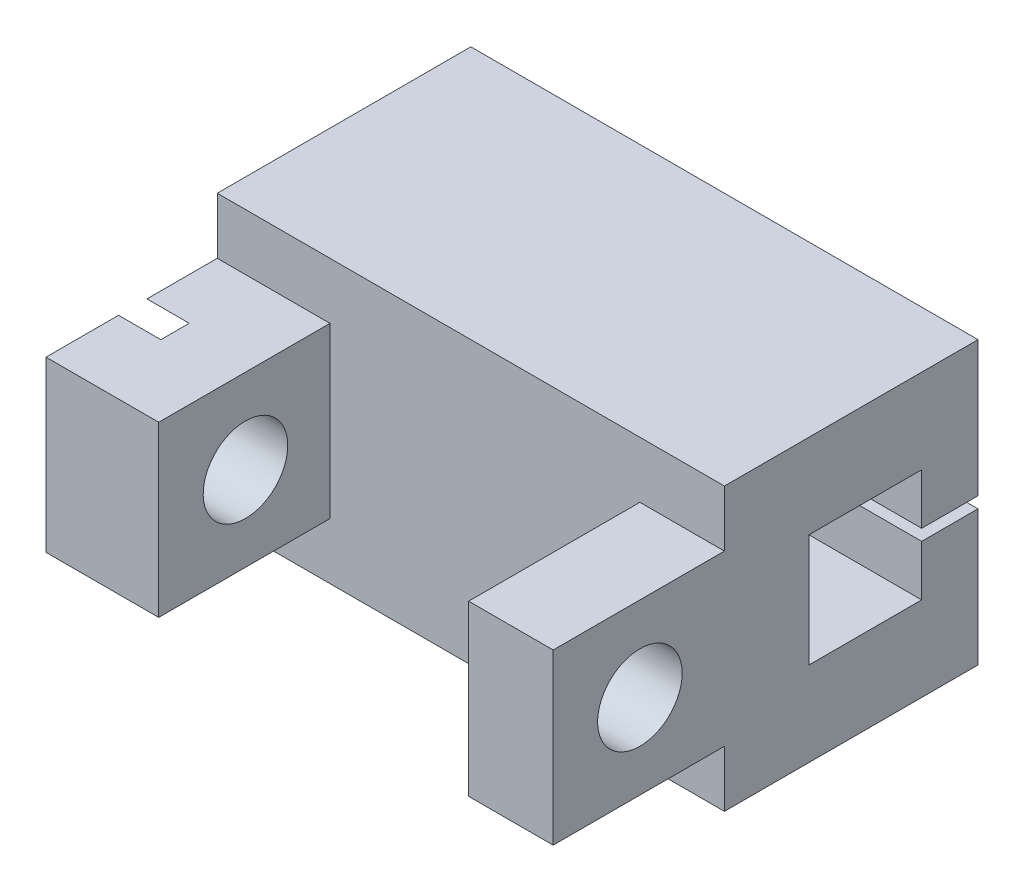
SolidWorks part; units mm, degrees
ref_plane "Alzado" through (0, 0, 0) normal (0, 0, 1) x (1, 0, 0)
ref_plane "Planta" through (0, 0, 0) normal (0, 1, 0) x (1, 0, 0)
ref_plane "Vista lateral" through (0, 0, 0) normal (1, 0, 0) x (0, 0, -1)
sketch "Croquis1" plane through (0, 0, 0) normal (0, 0, 1) x (1, 0, 0)
  line L1 (-7.9274, 1.7398) -> (10.0726, 1.7398)
  line L2 (-7.9274, 1.7398) -> (-7.9274, -8.2602)
  line L3 (-7.9274, -8.2602) -> (10.0726, -8.2602)
  line L4 (10.0726, 1.7398) -> (10.0726, -8.2602)
  dimension "D1" = 18
  dimension "D2" = 10
extrude "Saliente-Extruir1" add sketch "Croquis1" along normal blind 3
sketch "Croquis2" plane through (10.0726, 0, 0) normal (1, 0, 0) x (0, 0, -1)
  line L0 (-3, -8.2602) -> (-3, 1.7398) construction
  line L1 (-5.9993, -3.2602) -> (-3, -3.2602) construction
  line L3 (-3, -6.2602) -> (-9.0782, -6.2602)
  line L4 (-3, -6.2602) -> (-3, -0.2602)
  line L5 (-3, -0.2602) -> (-9.0782, -0.2602)
  line L6 (-9.0782, -6.2602) -> (-9.0782, -0.2602)
  circle A0 centre (-5.9993, -3.2602) radius 1.5
  dimension "D1" = 3
  dimension "D2" = 6
  dimension "D3" = 3
extrude "Saliente-Extruir2" add sketch "Croquis2" against normal blind 3
extrude "Saliente-Extruir3" add sketch "Croquis2<2>" along normal blind 4 from surface starting at face at (-7.9274, -3.2602, 1.5)
sketch "Croquis2<2>" plane through (10.0726, 0, 0) normal (1, 0, 0) x (0, 0, -1) same geometry as "Croquis2"
sketch "Croquis3" plane through (-7.9274, 0, 0) normal (-1, 0, 0) x (0, 0, 1)
  line L1 (5.9993, -6.5511) -> (8.8493, -4.9056)
  line L2 (8.8493, -4.9056) -> (8.8493, -1.6147)
  line L3 (8.8493, -1.6147) -> (5.9993, 0.0307)
  line L4 (5.9993, 0.0307) -> (3.1493, -1.6147)
  line L5 (3.1493, -1.6147) -> (3.1493, -4.9056)
  line L6 (3.1493, -4.9056) -> (5.9993, -6.5511)
  circle A0 centre (5.9993, -3.2602) radius 2.85 construction
  dimension "D1" = 5.7
extrude "Cortar-Extruir1" cut sketch "Croquis3" against normal blind 1.5
sketch "Croquis4" plane through (10.0726, 0, 0) normal (1, 0, 0) x (0, 0, -1)
  line L0 (0, -3.2602) -> (4.8296, -3.2602) construction
  line L1 (0, -8.2602) -> (0, 1.7398) construction
  line L2 (4, -1.2602) -> (4, -3.0602)
  line L3 (0, -8.2602) -> (6, -8.2602)
  line L4 (0, -8.2602) -> (0, -5.2602)
  line L5 (0, -5.2602) -> (4, -5.2602)
  line L6 (6, -8.2602) -> (6, -5.2602)
  line L8 (6, -5.2602) -> (6, -3.4602)
  line L9 (6, -3.4602) -> (4, -3.4602)
  line L10 (4, -5.2602) -> (4, -3.4602)
  line L11 (6, -3.0602) -> (4, -3.0602)
  line L12 (6, -1.2602) -> (6, -3.0602)
  line L13 (6, 1.7398) -> (6, -1.2602)
  line L14 (0, -1.2602) -> (4, -1.2602)
  line L15 (0, 1.7398) -> (0, -1.2602)
  line L16 (0, 1.7398) -> (6, 1.7398)
  dimension "D1" = 2
  dimension "D2" = 6
  dimension "D3" = 2
  dimension "D4" = 1.8
extrude "Saliente-Extruir4" add sketch "Croquis4" against normal up to vertex (18 mm away) up to point (-7.9274, -8.2602, 3)
